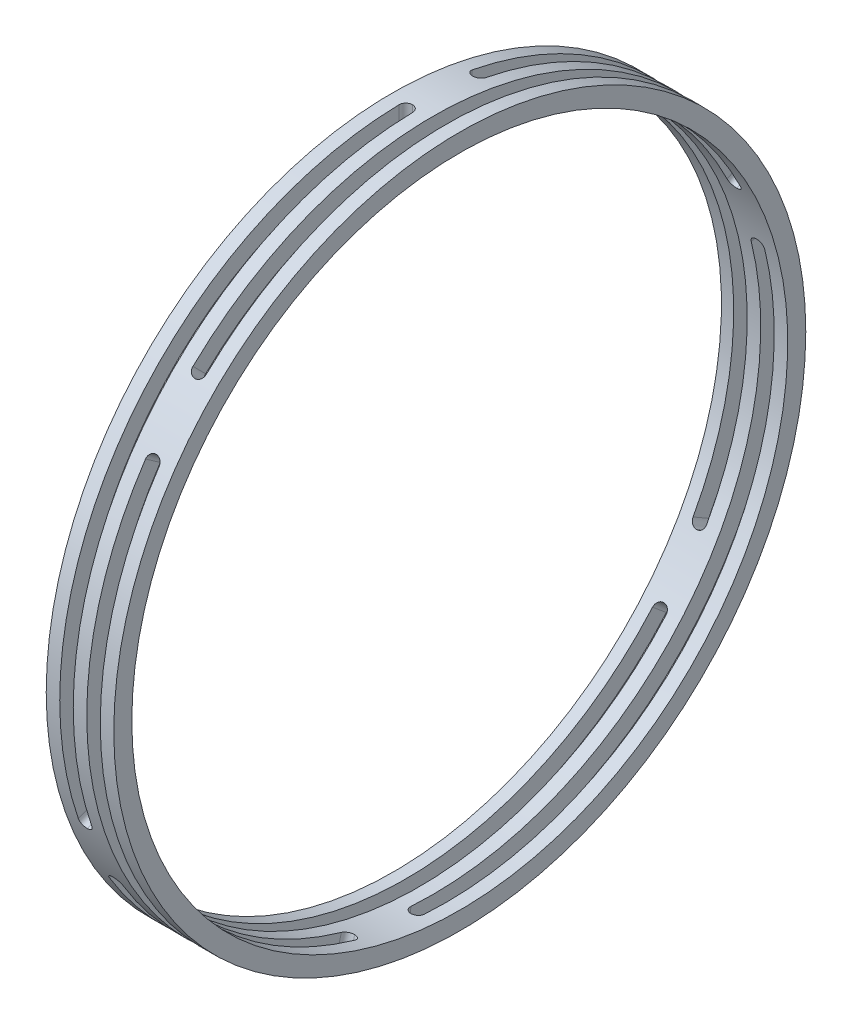
SolidWorks part; units mm, degrees
ref_plane "Přední rovina" through (0, 0, 0) normal (0, 0, 1) x (1, 0, 0)
ref_plane "Horní rovina" through (0, 0, 0) normal (0, 1, 0) x (1, 0, 0)
ref_plane "Pravá rovina" through (0, 0, 0) normal (1, 0, 0) x (0, 0, -1)
sketch "Skica1" plane through (0, 0, 0) normal (0, 0, 1) x (1, 0, 0)
  line L0 (0, 0) -> (71.8062, 0) construction
  line L1 (0, 38.4) -> (0.1399, 36.4)
  line L2 (0.1399, 36.4) -> (7.5, 36.4)
  line L3 (7.5, 36.4) -> (7.5, 38.4)
  line L4 (7.5, 38.4) -> (0, 38.4)
  dimension "D1" = 38.4
  dimension "D2" = 2
  dimension "D3" = 7.5
  dimension "D4" = 86
revolve "Rotovat1" add sketch "Skica1" angle 360 about L0
sketch "Skica3" plane through (0, 0, 0) normal (0, 0, 1) x (1, 0, 0)
  line L0 (7.5, 38.4) -> (0, 38.4) construction
  line L1 (1.5, 38.4) -> (3, 38.4)
  line L2 (1.5, 38.4) -> (1.5, 36.4)
  line L3 (1.5, 36.4) -> (3, 36.4)
  line L4 (3, 38.4) -> (3, 36.4)
  line L5 (0, 38.4) -> (0, -38.4) construction
  line L6 (0.1399, 36.4) -> (0.1399, -36.4) construction
  line L7 (0.1399, 36.4) -> (0.1399, -36.4) construction
  dimension "D1" = 1.5
  dimension "D2" = 1.5
revolve "Odebrat rotací1" cut sketch "Skica3" angle 110 about L0
fillet "Zaoblit1" radius 0.75 4 edges at (3, -12.7916, 35.1445) (1.5, -12.7916, 35.1445) (1.5, 37.4, 0) (3, 37.4, 0)
pattern_circular "Kruhové pole1" count 3 over 360 about axis through (0, 0, 0) along (1, 0, 0) of "Odebrat rotací1", "Zaoblit1"
ref_plane "Rovina1" through (0, 0, 0) normal (0, -0.8192, 0.5736) x (1, 0, 0)
sketch "Skica5" plane through (0, 0, 0) normal (0, -0.8192, 0.5736) x (1, 0, 0)
  line L0 (7.5, -38.4) -> (7.5, 38.4) construction
  line L1 (7.5, -38.4) -> (7.5, 38.4) construction
  line L2 (7.5, 38.4) -> (3, 38.4) construction
  line L3 (6, 38.4) -> (4.5, 38.4)
  line L4 (6, 38.4) -> (6, 36.4)
  line L5 (6, 36.4) -> (4.5, 36.4)
  line L6 (4.5, 38.4) -> (4.5, 36.4)
  dimension "D1" = 1.5
  dimension "D2" = 1.5
  dimension "D3" = 2
revolve "Odebrat rotací2" cut sketch "Skica5" angle 110 about L0
fillet "Zaoblit3" radius 0.75 4 edges at (4.5, 21.4518, 30.6363) (6, 21.4518, 30.6363) (6, -36.1256, 9.6798) (4.5, -36.1256, 9.6798)
pattern_circular "Kruhové pole2" count 3 over 360 about axis through (0, 0, 0) along (1, 0, 0) of "Odebrat rotací2", "Zaoblit3"
